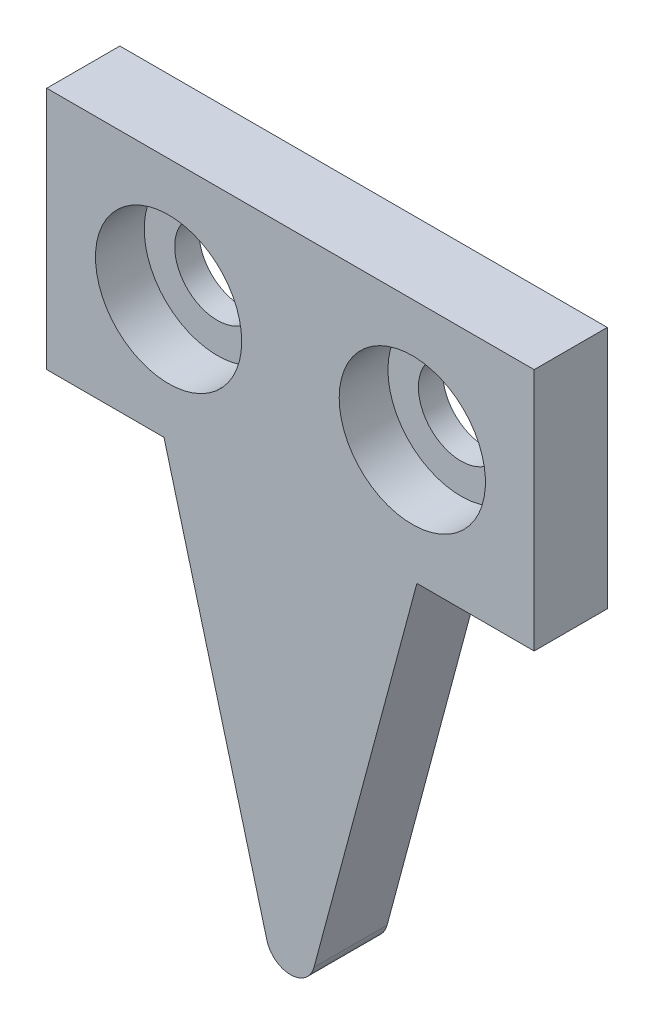
SolidWorks part; units mm, degrees
ref_plane "Front Plane" through (0, 0, 0) normal (0, 0, 1) x (1, 0, 0)
ref_plane "Top Plane" through (0, 0, 0) normal (0, 1, 0) x (1, 0, 0)
ref_plane "Right Plane" through (0, 0, 0) normal (1, 0, 0) x (0, 0, -1)
sketch "Sketch2" plane through (0, 0, 0) normal (0, 0, 1) x (1, 0, 0)
  line L1 (-5.1885, 15.5) -> (-0.9659, -0.2588)
  line L3 (0, -11.1651) -> (0, 29.6028) construction
  line L6 (-5.1885, 15.5) -> (-10, 15.5)
  line L7 (-10, 15.5) -> (-10, 25.5)
  line L8 (-10, 25.5) -> (10, 25.5)
  line L9 (10, 15.5) -> (10, 25.5)
  line L10 (5.1885, 15.5) -> (10, 15.5)
  line L11 (5.1885, 15.5) -> (0.9659, -0.2588)
  arc A0 (-0.9659, -0.2588) -> (0.9659, -0.2588) centre (0, 0) ccw
  point P5 (0, 25.5)
  point P11 (0, 25.5)
  point P13 (0, -1)
  dimension "D4" = 1
  dimension "D1" = 10
  dimension "D2" = 16.5
  dimension "D3" = 20
  dimension "D5" = 105
extrude "Boss-Extrude1" add sketch "Sketch2" along normal blind 3
sketch "Sketch3" plane through (0, 0, 3) normal (0, 0, 1) x (1, 0, 0)
  line L3 (-10, 25.5) -> (-10, 15.5) construction
  line L4 (0, -1) -> (0, 25.5) construction
  line L5 (10, 25.5) -> (-10, 25.5) construction
  circle A0 centre (-5, 20.5) radius 1.75
  arc A1 (-0.9659, -0.2588) -> (0.9659, -0.2588) centre (0, 0) ccw construction
  circle A2 centre (5, 20.5) radius 1.75
  point P9 (-10, 20.5)
  dimension "D1" = 3.5
  dimension "D2" = 5
  dimension "D3" = 5
extrude "Cut-Extrude1" cut sketch "Sketch3" against normal up to surface (3 mm away) up to face at (0, 13.9676, 0)
sketch "Sketch5" plane through (0, 0, 3) normal (0, 0, 1) x (1, 0, 0)
  line L0 (0, -1) -> (0, 25.5) construction
  line L1 (10, 25.5) -> (-10, 25.5) construction
  line L2 (-10, 25.5) -> (-10, 15.5) construction
  arc A0 (-0.9659, -0.2588) -> (0.9659, -0.2588) centre (0, 0) ccw construction
  circle A1 centre (-5, 20.5) radius 3
  circle A2 centre (5, 20.5) radius 3
  point P12 (-10, 20.5)
  dimension "D1" = 6
  dimension "D2" = 5
extrude "Cut-Extrude2" cut sketch "Sketch5" against normal blind 2
